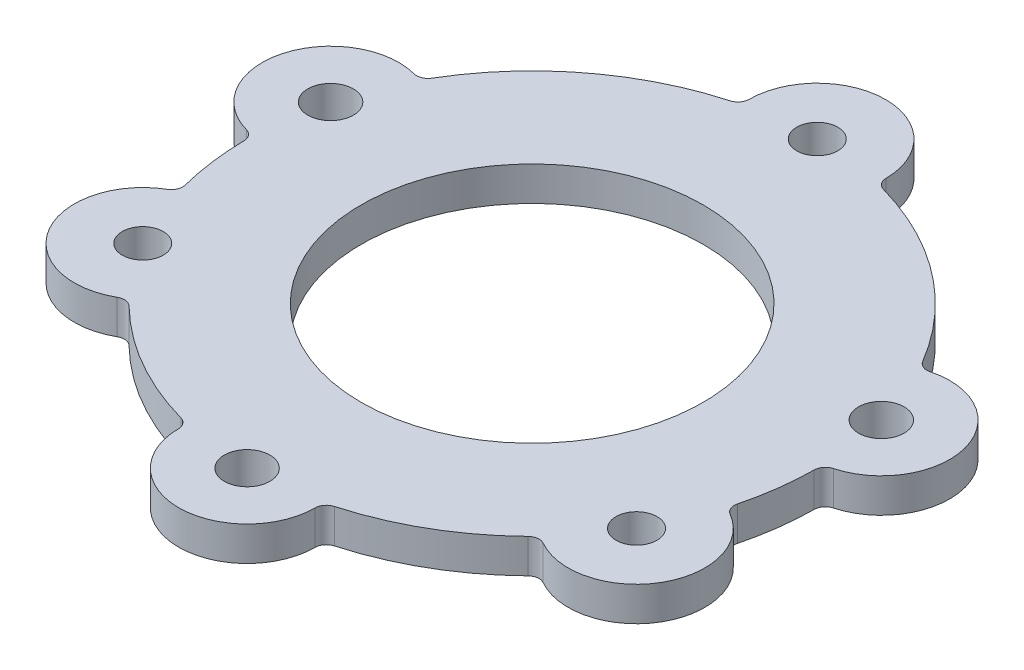
SolidWorks part; units mm, degrees
material "Delrin 2700 NC010, Low Viscosity Acetal Copolymer (SS)"
ref_plane "Front" through (0, 0, 0) normal (0, 0, 1) x (1, 0, 0)
ref_plane "Top" through (0, 0, 0) normal (0, 1, 0) x (1, 0, 0)
ref_plane "Right" through (0, 0, 0) normal (1, 0, 0) x (0, 0, -1)
sketch "Sketch1" plane through (0, 0, 0) normal (0, 1, 0) x (1, 0, 0)
  line L0 (-3, 0) -> (3, 0) construction
  line L5 (0, 0) -> (0, -12.5) construction
  line L8 (3, 0) -> (3, -12.5)
  line L9 (-3, 0) -> (-3, -12.5)
  line L12 (0, 0) -> (0, 12.5) construction
  line L15 (3, 0) -> (3, 12.5)
  line L18 (-3, 0) -> (-3, 12.5)
  line L21 (-1.5, -2.5981) -> (9.3253, -8.8481)
  line L24 (1.5, 2.5981) -> (12.3253, -3.6519)
  line L25 (0, 0) -> (10.8253, -6.25) construction
  line L26 (-1.5, 2.5981) -> (-12.3253, -3.6519)
  line L27 (1.5, -2.5981) -> (-9.3253, -8.8481)
  line L28 (0, 0) -> (-10.8253, -6.25) construction
  line L35 (0, 0) -> (-12.0741, 3.2352) construction
  line L36 (-0.7765, -2.8978) -> (-12.8505, 0.3375)
  line L37 (0.7765, 2.8978) -> (-11.2976, 6.133)
  line L38 (0, 25.1874) -> (0, -25.1874) construction
  line L39 (0, 0) -> (12.0741, 3.2352) construction
  line L40 (0.7765, -2.8978) -> (12.8505, 0.3375)
  line L41 (-0.7765, 2.8978) -> (11.2976, 6.133)
  circle A1 centre (0, 0) radius 7.5
  arc A11 (3, 0) -> (-3, 0) centre (0, 0) ccw
  arc A12 (-3, -12.5) -> (3, -12.5) centre (0, -12.5) ccw
  circle A13 centre (0, -12.5) radius 1
  circle A21 centre (0, 0) radius 12.5
  arc A22 (3, 0) -> (-3, 0) centre (0, 0) cw
  arc A23 (-3, 12.5) -> (3, 12.5) centre (0, 12.5) cw
  circle A24 centre (0, 12.5) radius 0.9
  arc A25 (12.3253, -3.6519) -> (9.3253, -8.8481) centre (10.8253, -6.25) cw
  arc A26 (-1.5, -2.5981) -> (1.5, 2.5981) centre (0, 0) cw
  circle A27 centre (10.8253, -6.25) radius 0.9
  arc A28 (-9.3253, -8.8481) -> (-12.3253, -3.6519) centre (-10.8253, -6.25) cw
  arc A29 (-1.5, 2.5981) -> (1.5, -2.5981) centre (0, 0) cw
  circle A30 centre (-10.8253, -6.25) radius 0.9
  arc A31 (-0.7765, -2.8978) -> (0.7765, 2.8978) centre (0, 0) ccw
  arc A32 (-11.2976, 6.133) -> (-12.8505, 0.3375) centre (-12.0741, 3.2352) ccw
  circle A33 centre (-12.0741, 3.2352) radius 1
  circle A35 centre (12.0741, 3.2352) radius 1
  arc A36 (0.7765, -2.8978) -> (-0.7765, 2.8978) centre (0, 0) cw
  arc A37 (11.2976, 6.133) -> (12.8505, 0.3375) centre (12.0741, 3.2352) cw
  point P7 (0, 6.25)
  point P10 (0, -6.25)
  point P20 (-6.037, 1.6176)
  point P25 (-5.4127, -3.125)
  point P27 (5.4127, -3.125)
  point P30 (0, -15.5)
  point P37 (-5.4127, -3.125)
  point P38 (-5.4127, 3.125)
  point P52 (0, 0)
  point P55 (6.037, 1.6176)
  point P71 (-5.4127, -3.125)
  point P78 (-5.4127, 3.125)
  dimension "D2" = 15
  dimension "D6" = 3
  dimension "D7" = 2
  dimension "D5" = 25
  dimension "D1" = 1.8
  dimension "D4" = 2
  dimension "D8" = 12.5
  dimension "D3" = 75
extrude "Boss-Extrude1" add sketch "Sketch1" along normal blind 1.5 contours A24 A21 L15 A23 L18 | A24 A21 L18 A1 L15 | L41 A21 L15 A1 | A21 A35 L41 A1 L24 L40 | A37 L41 A21 A35 L40 | L24 A21 L40 | A1 L40 L24 | A27 A21 L24 L40 A1 L21 | A27 A21 L21 A25 L24 | L8 A21 L21 A1 | A13 A21 L8 A1 L9 | A21 A13 L9 A12 L8 | L27 A21 L9 A1 | A30 A21 L27 A1 L36 L26 | A30 A21 L26 A28 L27 | A1 L26 L36 | L36 A21 L26 | A33 A21 L36 L26 A1 L37 | A33 A21 L37 A32 L36 | L18 A21 L37 A1 region at (7.5477, 0, 0.9937) region at (8.4341, 0, 4.8749) region at (9.3876, 0, -2.5204) region at (5.2055, 0, 9.0162) region at (0, 0, 9.7156) region at (10.8216, 0, 1.4247) region at (0, 0, -9.7371) region at (6.1903, 0, -8.0673) region at (0, 0, 13.8006) region at (-5.2055, 0, 9.0162) region at (11.9378, 0, 6.8923) region at (13.3304, 0, -3.5719) region at (0, 0, -13.7846) region at (-6.1903, 0, -8.0673) region at (-8.4341, 0, 4.8749) region at (-9.3876, 0, -2.5204) region at (-11.9378, 0, 6.8923) region at (-7.5477, 0, 0.9937) region at (-13.3304, 0, -3.5719) region at (-10.8216, 0, 1.4247)
fillet "Fillet1" radius 0.5 12 edges at (-3, 0.75, 12.1347) (3, 0.75, 12.1347) (9.0089, 0.75, 8.6654) (12.0089, 0.75, 3.4693) (12.4976, 0.75, -0.2429) (10.9447, 0.75, -6.0385) (3, 0.75, -12.1347) (-3, 0.75, -12.1347) (-10.9447, 0.75, -6.0385) (-12.4976, 0.75, -0.2429) (-12.0089, 0.75, 3.4693) (-9.0089, 0.75, 8.6654)
equation "\"PostAngle\"=75"
equation "\"D3@Sketch1\"=\"PostAngle\""
